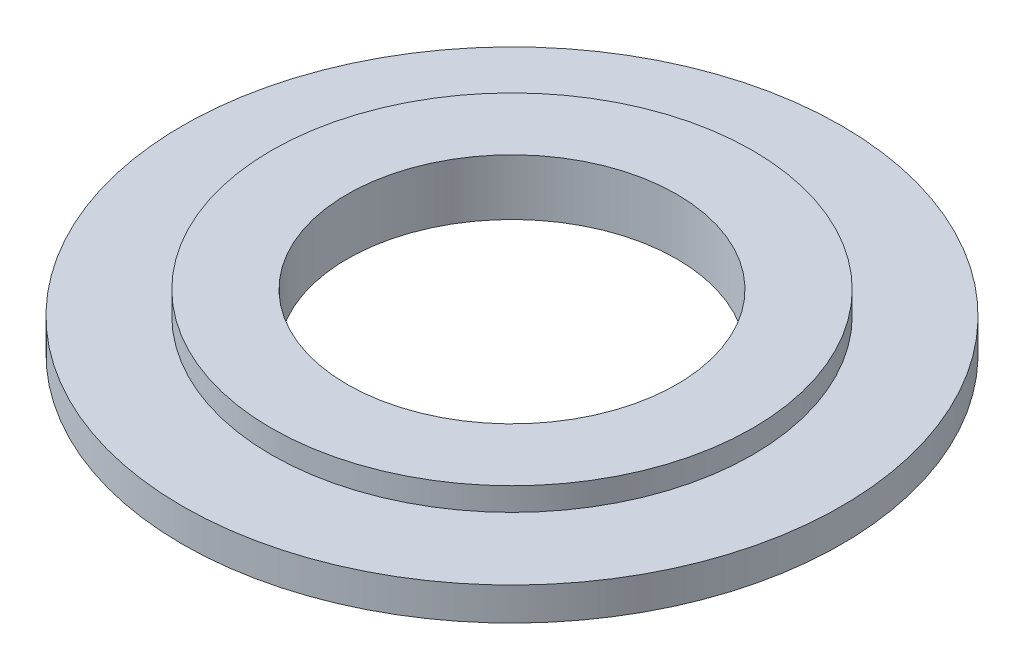
SolidWorks part; units mm, degrees
ref_plane "Front Plane" through (0, 0, 0) normal (0, 0, 1) x (1, 0, 0)
ref_plane "Top Plane" through (0, 0, 0) normal (0, 1, 0) x (1, 0, 0)
ref_plane "Right Plane" through (0, 0, 0) normal (1, 0, 0) x (0, 0, -1)
sketch "Sketch1" plane through (0, 0, 0) normal (0, 1, 0) x (1, 0, 0)
  circle A0 centre (0, 0) radius 5
  circle A1 centre (0, 0) radius 7.3
  circle A2 centre (0, 0) radius 10
  dimension "D1" = 14.6
  dimension "D2" = 10
  dimension "D3" = 20
extrude "Boss-Extrude1" add sketch "Sketch1" against normal blind 1 contours A2 A1 | A1 A0 region at (-7.0935, 0, 0) region at (-9.7172, 0, 0)
extrude "Boss-Extrude2" add sketch "Sketch1<3>" along normal blind 0.7 contours A1 A0 region at (-7.0935, 0, 0)
sketch "Sketch1<3>" plane through (0, 0, 0) normal (0, 1, 0) x (1, 0, 0) same geometry as "Sketch1"
